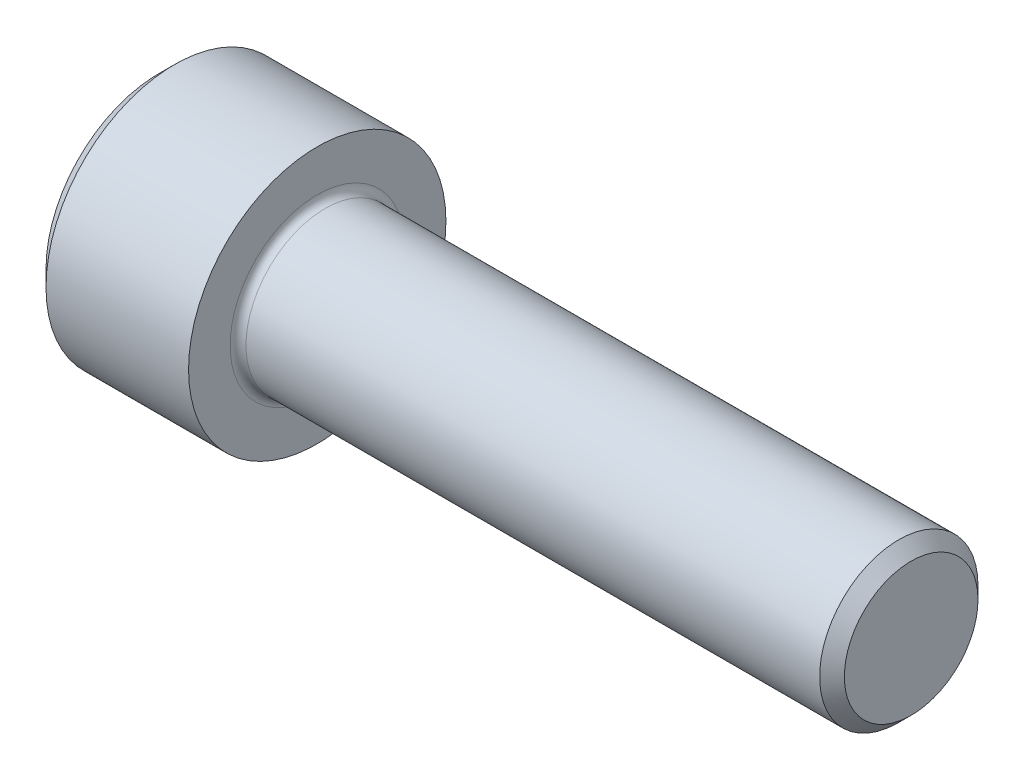
SolidWorks part; units mm, degrees
material "NA"
ref_plane "Front Plane" through (0, 0, 0) normal (0, 0, 1) x (1, 0, 0)
ref_plane "Top Plane" through (0, 0, 0) normal (0, 1, 0) x (1, 0, 0)
ref_plane "Right Plane" through (0, 0, 0) normal (1, 0, 0) x (0, 0, -1)
sketch "Sketch1" plane through (0, 0, 0) normal (0, 1, 0) x (1, 0, 0)
  line L0 (0, 0) -> (0, 6.5)
  line L1 (0, 6.5) -> (8, 6.5)
  line L2 (8, 6.5) -> (8, 4)
  line L3 (8, 4) -> (38, 4)
  line L4 (38, 4) -> (38, 0)
  line L5 (38, 0) -> (0, 0)
  dimension "16" = 8
  dimension "D2" = 6.5
  dimension "D3" = 4
  dimension "20" = 30
revolve "Revolve1" add sketch "Sketch1" angle 360 about L5
chamfer "Chamfer1" distance 0.625 angle 45 1 edges at (38, 0, -4)
sketch "Sketch3" plane through (0, 0, 0) normal (0, 1, 0) x (1, 0, 0)
  line L0 (0, 0) -> (5.7321, 0)
  line L1 (0, 6.5) -> (0, -6.5) construction
  line L2 (5.7321, 0) -> (4, 3)
  line L3 (4, 3) -> (0, 3)
  line L4 (0, 3) -> (0, 0)
  dimension "5" = 3
  dimension "D2" = 4
  dimension "D3" = 60
revolve "Cut-Revolve1" cut sketch "Sketch3" angle 360 about L0
sketch "Sketch2" plane through (0, 0, 0) normal (-1, 0, 0) x (0, 0, 1)
  line L0 (0, 0) -> (0, 3.4641) construction
  line L1 (0, 3.4641) -> (-3, 1.7321)
  line L2 (-3, 1.7321) -> (-3, -1.7321)
  line L3 (-3, -1.7321) -> (0, -3.4641)
  line L4 (0, -3.4641) -> (3, -1.7321)
  line L5 (3, -1.7321) -> (3, 1.7321)
  line L6 (3, 1.7321) -> (0, 3.4641)
  circle A0 centre (0, 0) radius 3 construction
  dimension "4" = 6
extrude "Cut-Extrude1" cut sketch "Sketch2" against normal blind 4 contours L4 L5 L6 L1 L2 L3
chamfer "Chamfer2" distance 0.8 angle 45 1 edges at (0, 0, -6.5)
fillet "Fillet1" radius 0.4 1 edges at (8, 0, -4)
ref_plane "Plane1" through (39.6, 0, 0) normal (1, 0, 0) x (0, 0, -1)
sketch "Sketch5" plane through (39.6, 0, 0) normal (1, 0, 0) x (0, 0, -1)
  circle A0 centre (0, 0) radius 4
  dimension "D1" = 8
curve "Helix/Spiral1" pitch 1.25 height 30 turns 24
sketch "Sketch6" plane through (0, 0, 0) normal (0, 0, 1) x (1, 0, 0)
  line L0 (38.9873, 4.1353) -> (39.6, 3.0524) construction
  line L1 (39.6, 3.0524) -> (40.2127, 4.1353) construction
  line L2 (40.2127, 4.1353) -> (38.9873, 4.1353) construction
  line L3 (39.6, 4.1353) -> (39.6, 3.0524) construction
  line L4 (39.0639, 4) -> (40.1361, 4)
  line L5 (39.0639, 4) -> (39.4469, 3.323)
  line L6 (39.7531, 3.323) -> (40.1361, 4)
  line L7 (39.7531, 3.323) -> (39.4469, 3.323)
  point P6 (39.6, 4)
  dimension "D1" = 59
  dimension "D2" = 0.677
  dimension "D3" = 0.1353
  dimension "D4" = 0.2706
sweep "Cut-Sweep2" [suppressed] cut profiles "Sketch6" path "Helix/Spiral1"
